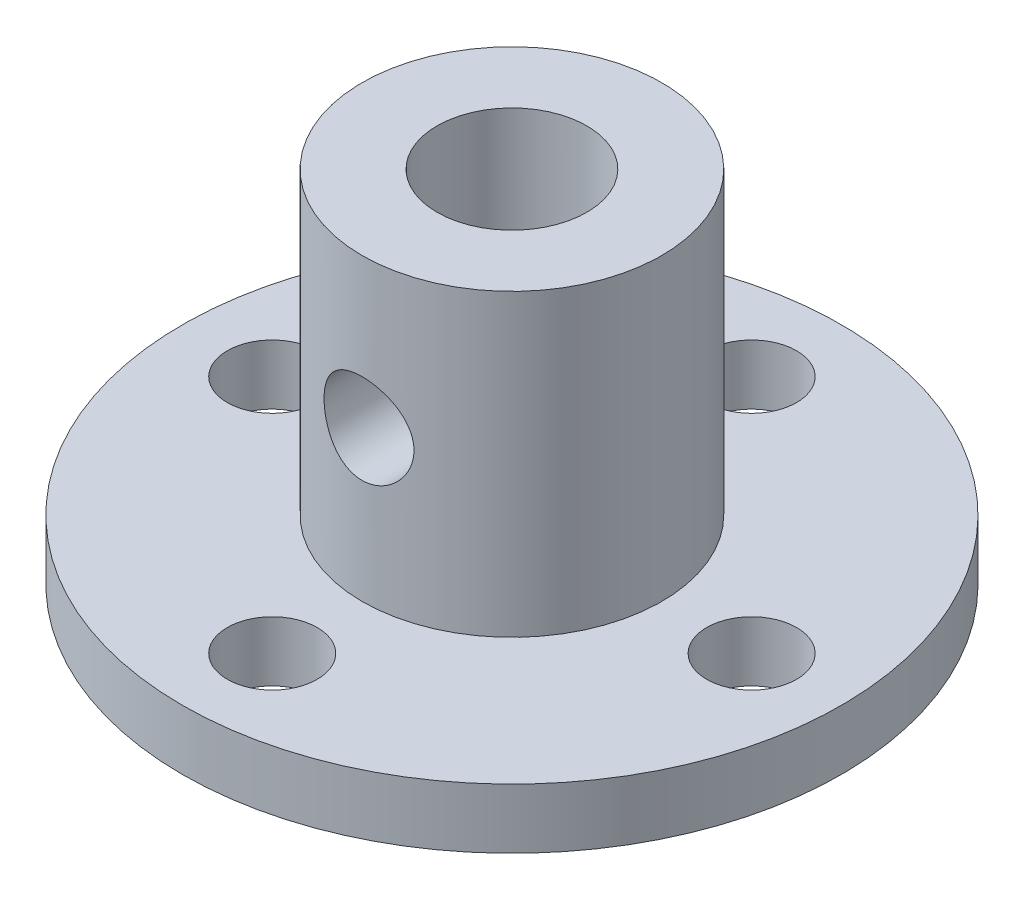
SolidWorks part; units mm, degrees
material "不锈钢 (铁素体)"
ref_plane "前视基准面" through (0, 0, 0) normal (0, 0, 1) x (1, 0, 0)
ref_plane "上视基准面" through (0, 0, 0) normal (0, 1, 0) x (1, 0, 0)
ref_plane "右视基准面" through (0, 0, 0) normal (1, 0, 0) x (0, 0, -1)
other "Configuration Table"
sketch "草图1" plane through (0, 0, 0) normal (0, 1, 0) x (1, 0, 0)
  circle A0 centre (0, 0) radius 11
extrude "凸台-拉伸1" add sketch "草图1" along normal blind 2
sketch "草图2" plane through (0, 0, 0) normal (0, -1, 0) x (1, 0, 0)
  circle A0 centre (0, 0) radius 8 construction
  circle A1 centre (0, -8) radius 1.5
  circle A2 centre (8, 0) radius 1.5
  circle A3 centre (-8, 0) radius 1.5
  circle A4 centre (0, 8) radius 1.5
  dimension "D1" = 3
  dimension "D2" = 16
extrude "切除-拉伸1" cut sketch "草图2" against normal blind 2
sketch "草图3" plane through (0, 2, 0) normal (0, 1, 0) x (1, 0, 0)
  circle A0 centre (0, 0) radius 5
extrude "凸台-拉伸2" add sketch "草图3" along normal blind 10
sketch "草图4" plane through (0, 12, 0) normal (0, 1, 0) x (1, 0, 0)
  circle A0 centre (0, 0) radius 2.5
  dimension "D1" = 5
extrude "切除-拉伸2" cut sketch "草图4" against normal blind 12
sketch "草图5" plane through (0, 0, 0) normal (0, 0, 1) x (1, 0, 0)
  line L0 (0, 2) -> (0, 12) construction
  line L1 (11, 2) -> (-11, 2) construction
  line L2 (5, 12) -> (-5, 12) construction
  circle A0 centre (0, 7) radius 1.5
  dimension "D1" = 3
extrude "切除-拉伸4" cut sketch "草图5" against normal blind 5 and the other way blind 5
ref_plane "基准面1" through (0, 0, 5) normal (0, 0, 1) x (1, 0, 0)
